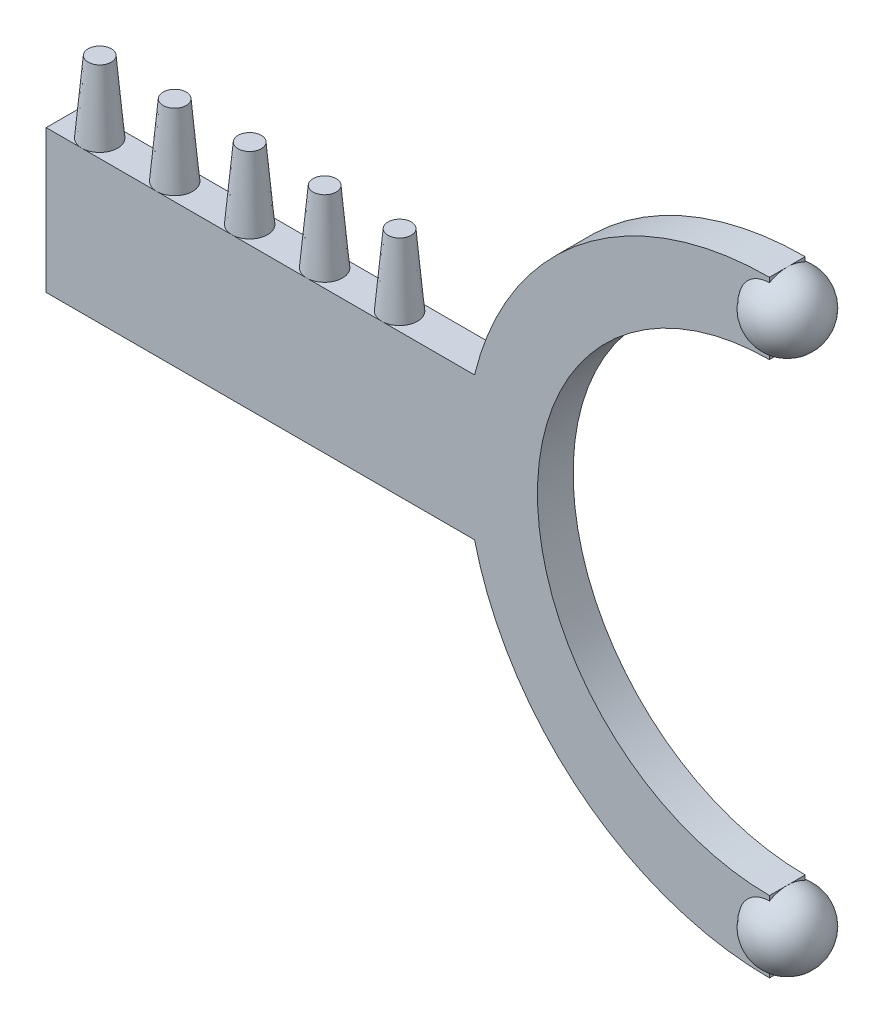
SolidWorks part; units mm, degrees
ref_plane "Front Plane" through (0, 0, 0) normal (0, 0, 1) x (1, 0, 0)
ref_plane "Top Plane" through (0, 0, 0) normal (0, 1, 0) x (1, 0, 0)
ref_plane "Right Plane" through (0, 0, 0) normal (1, 0, 0) x (0, 0, -1)
sketch "Sketch1" plane through (0, 0, 0) normal (0, 0, 1) x (1, 0, 0)
  line L0 (-20.2614, 2) -> (-20.2614, -2)
  line L1 (-8.2614, 2) -> (-20.2614, 2)
  line L2 (-8.2614, -2) -> (-20.2614, -2)
  line L4 (0, -6.5) -> (0, -8.5)
  line L5 (0, 8.5) -> (0, 6.5)
  line L6 (0, 0) -> (0, 2.8656) construction
  arc A0 (0, 6.5) -> (0, -6.5) centre (0, 0) ccw
  arc A1 (0, 8.5) -> (0, -8.5) centre (0, 0) ccw
  arc A4 (0, 8.5) -> (0, 6.5) centre (0, 7.5) ccw
  arc A5 (0, -6.5) -> (0, -8.5) centre (0, -7.5) ccw
  point P5 (-6.5, 0)
  point P11 (-20.2614, 0)
  point P12 (-8.5, 0)
  point P17 (0, 0)
  dimension "D1" = 6.5
  dimension "D2" = 8.5
  dimension "D3" = 2
  dimension "D5" = 4
  dimension "D6" = 12
extrude "Boss-Extrude1" add sketch "Sketch1" along normal mid plane 1 contours A1 L1 L0 L2 | L5 A1 L4 A0 | L5 A4 | L4 A5 region at (-14.3409, 0, 0) region at (-5.1384, 6.5308, 0) region at (-0.4244, 7.5, 0) region at (-0.4244, -7.5, 0)
revolve "Revolve14" add sketch "Sketch1<7>" angle 360 about L6 region at (-0.4244, 7.5, 0) region at (-0.4244, -7.5, 0)
sketch "Sketch1<7>" plane through (0, 0, 0) normal (0, 0, 1) x (1, 0, 0) same geometry as "Sketch1"
sketch "Sketch2" plane through (0, 2, 0) normal (0, 1, 0) x (1, 0, 0)
  line L0 (-20.2614, -0.5) -> (-20.2614, 0.5) construction
  circle A0 centre (-19.2614, 0) radius 0.5
  circle A1 centre (-17.1614, 0) radius 0.5
  circle A2 centre (-15.0614, 0) radius 0.5
  circle A3 centre (-12.9614, 0) radius 0.5
  circle A4 centre (-10.8614, 0) radius 0.5
  point P4 (-20.2614, 0)
  dimension "D1" = 1
  dimension "D2" = 1
  dimension "D3" = 5
extrude "Boss-Extrude2" add sketch "Sketch2" along normal blind 2 draft 5
